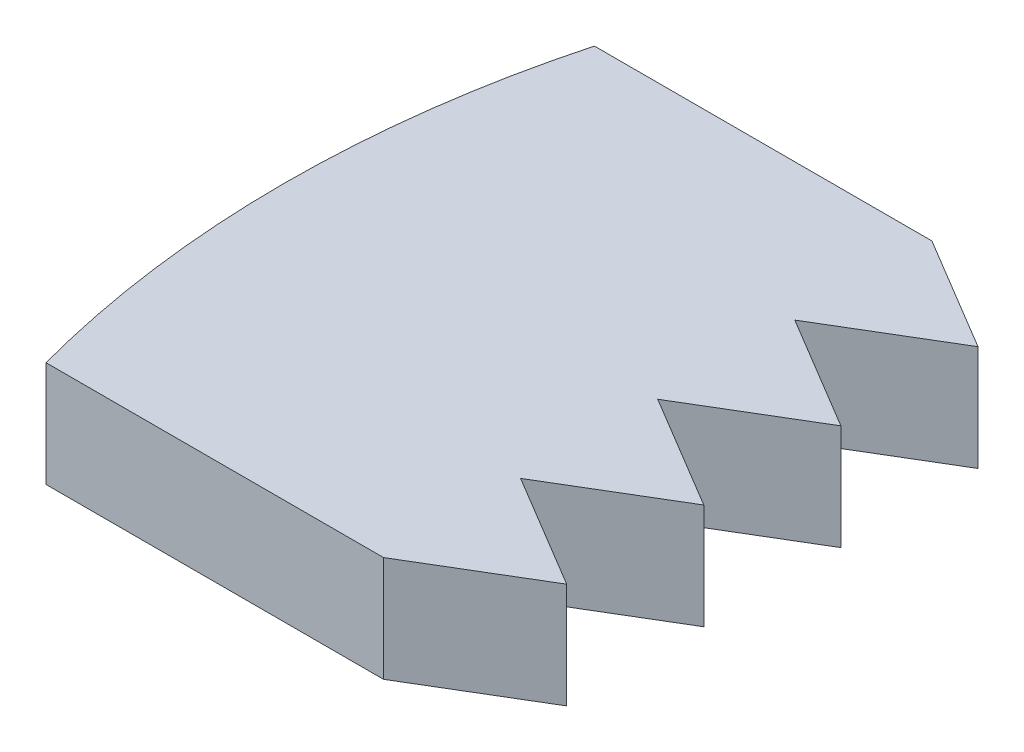
SolidWorks part; units mm, degrees
ref_plane "Front Plane" through (0, 0, 0) normal (0, 0, 1) x (1, 0, 0)
ref_plane "Top Plane" through (0, 0, 0) normal (0, 1, 0) x (1, 0, 0)
ref_plane "Right Plane" through (0, 0, 0) normal (1, 0, 0) x (0, 0, -1)
sketch "Sketch1" plane through (0, 0, 0) normal (0, 1, 0) x (1, 0, 0)
  line L0 (-22.9891, 27.3062) -> (-18.8469, 24.8297)
  line L1 (-18.8469, 24.8297) -> (-22.9891, 22.3532)
  line L2 (-22.9891, 22.3532) -> (-18.8469, 19.8767)
  line L3 (-18.8469, 19.8767) -> (-22.9891, 17.4002)
  line L4 (-22.9891, 17.4002) -> (-18.8469, 14.9237)
  line L5 (-18.8469, 14.9237) -> (-22.9891, 12.4472)
  line L6 (-22.9891, 12.4472) -> (-18.8469, 9.9707)
  line L7 (-18.8469, 9.9707) -> (-22.9891, 7.4942)
  line L8 (-22.9891, 7.4942) -> (-35.1811, 7.4942)
  line L10 (-35.1811, 27.3062) -> (-22.9891, 27.3062)
  line L11 (-22.9891, 17.4002) -> (-34.8407, 17.4002) construction
  arc A1 (-35.1811, 27.3062) -> (-35.1811, 7.4942) centre (1.6086, 17.4002) ccw
  dimension "D4" = 76.2
  dimension "D3" = 12.192
  dimension "D1" = 4.826
  dimension "D2" = 4.953
extrude "Boss-Extrude1" add sketch "Sketch1" along normal blind 3.81
